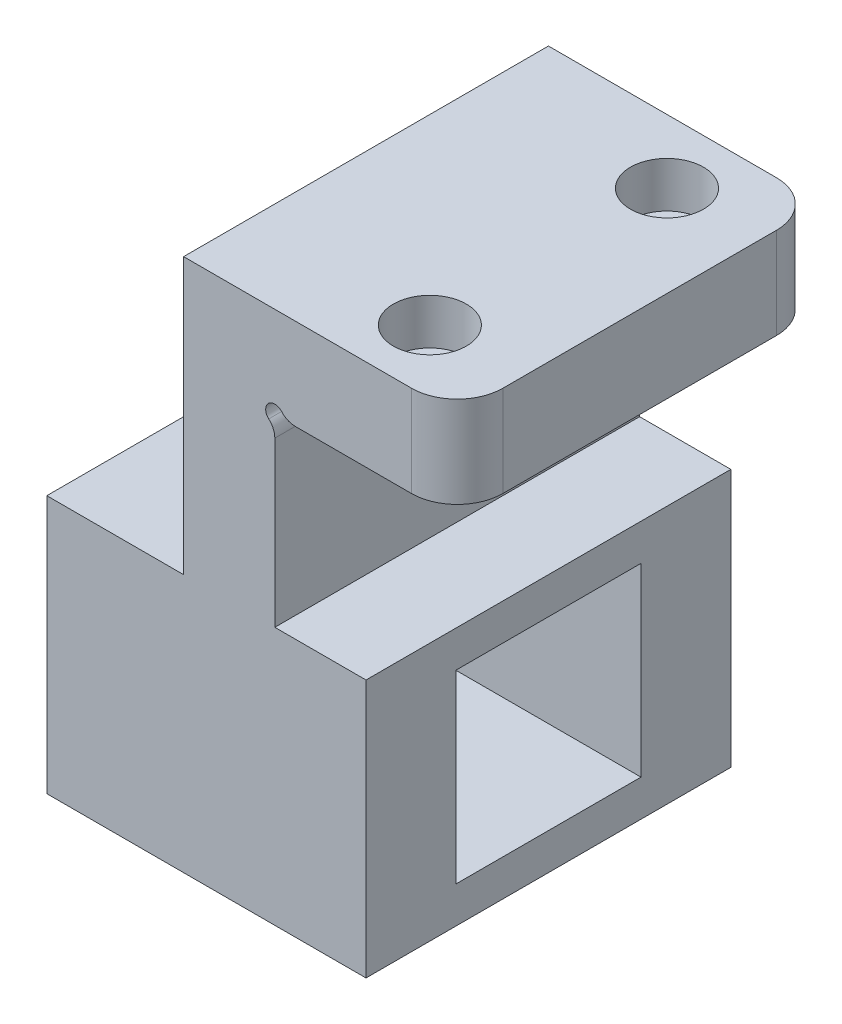
SolidWorks part; units mm, degrees
material "ABS"
ref_plane "Płaszczyzna przednia" through (0, 0, 0) normal (0, 0, 1) x (1, 0, 0)
ref_plane "Płaszczyzna górna" through (0, 0, 0) normal (0, 1, 0) x (1, 0, 0)
ref_plane "Płaszczyzna prawa" through (0, 0, 0) normal (1, 0, 0) x (0, 0, -1)
sketch "Szkic1" plane through (0, 0, 0) normal (0, 0, 1) x (1, 0, 0)
  line L0 (0, 0) -> (0, 19.7639)
  line L1 (2.2361, 22) -> (20, 22)
  line L2 (20, 22) -> (20, 32)
  line L3 (20, 32) -> (-10, 32)
  line L4 (-10, 32) -> (-10, 0)
  line L5 (-10, 0) -> (0, 0)
  arc A0 (0.7454, 22.6667) -> (-0.6667, 21.2546) centre (0, 22) ccw
  arc A1 (2.2361, 22) -> (0.7454, 22.6667) centre (2.2361, 24) cw
  arc A2 (0, 19.7639) -> (-0.6667, 21.2546) centre (-2, 19.7639) ccw
  dimension "D5" = 2
  dimension "D6" = 2
  dimension "D1" = 22
  dimension "D2" = 20
  dimension "D3" = 10
  dimension "D4" = 10
  dimension "D7" = 20
  dimension "D8" = 22
extrude "Dodanie-wyciągnięcie1" add sketch "Szkic1" along normal blind 40 contours L0 A2 A0 A1 L1 L2 L3 L4 L5
sketch "Szkic7" plane through (-10, 0, 0) normal (-1, 0, 0) x (0, 0, 1)
  line L4 (0, 19.7639) -> (0, 0)
  line L5 (40, 19.7639) -> (0, 19.7639)
  line L6 (40, 0) -> (40, 19.7639)
  line L7 (0, 0) -> (40, 0)
  line L8 (0, 19.7639) -> (0, 0)
  line L9 (40, 19.7639) -> (0, 19.7639)
  line L10 (40, 0) -> (40, 19.7639)
  line L11 (0, 0) -> (40, 0)
  circle A0 centre (20, 10) radius 4
  point P7 (20, 0)
  dimension "D2" = 8
  dimension "D3" = 10
  dimension "D1" = 0
extrude "Wytnij-wyciągnięcie2" cut sketch "Szkic7" against normal blind 5 contours A0 region at (-10, 10, 20)
sketch "Szkic8" plane through (-5, 0, 0) normal (-1, 0, 0) x (0, 0, 1)
  circle A0 centre (20, 10) radius 4 construction
  circle A1 centre (20, 10) radius 4
  circle A2 centre (20, 10) radius 2.1
  dimension "D1" = 4.2
extrude "Wytnij-wyciągnięcie3" cut sketch "Szkic8" against normal blind 5 contours A2 region at (-5, 10, 20)
sketch "Szkic9" plane through (0, 32, 0) normal (0, 1, 0) x (1, 0, 0)
  line L4 (20, 0) -> (2.2361, 0)
  line L5 (20, -40) -> (20, 0)
  line L6 (2.2361, -40) -> (20, -40)
  line L7 (2.2361, 0) -> (2.2361, -40)
  line L8 (20, 0) -> (2.2361, 0)
  line L9 (20, -40) -> (20, 0)
  line L10 (2.2361, -40) -> (20, -40)
  line L11 (2.2361, 0) -> (2.2361, -40)
  circle A0 centre (10, -7) radius 4
  circle A1 centre (10, -33) radius 4
  dimension "D3" = 8
  dimension "D2" = 10
  dimension "D4" = 7
  dimension "D5" = 7
  dimension "D1" = 0
extrude "Wytnij-wyciągnięcie4" cut sketch "Szkic9" against normal blind 5 contours A1 | A0 region at (10, 32, 7) region at (10, 32, 33)
sketch "Szkic10" plane through (0, 27, 0) normal (0, 1, 0) x (1, 0, 0)
  circle A0 centre (10, -7) radius 4 construction
  circle A1 centre (10, -33) radius 4 construction
  circle A2 centre (10, -7) radius 4
  circle A3 centre (10, -33) radius 4
  circle A4 centre (10, -7) radius 2.1
  circle A5 centre (10, -33) radius 2.1
  dimension "D1" = 4.2
extrude "Wytnij-wyciągnięcie5" cut sketch "Szkic10" against normal blind 5 contours A5 | A4 region at (10, 27, 7) region at (10, 27, 33)
fillet "Zaokrąglenie1" radius 5 2 edges at (20, 27, 0) (20, 27, 40)
ref_plane "Płaszczyzna1" through (0, 0, 20) normal (0, 0, 1) x (1, 0, 0)
sketch "Sketch1" plane through (-10, 0, 0) normal (-1, 0, 0) x (0, 0, 1)
  line L0 (20, 64.3239) -> (20, 19.1441) construction
  line L1 (9.85, -2.2) -> (30.15, -2.2)
  line L2 (9.85, -2.2) -> (9.85, -22.5)
  line L3 (9.85, -22.5) -> (30.15, -22.5)
  line L4 (30.15, -2.2) -> (30.15, -22.5)
  line L5 (0, 32) -> (0, 0) construction
  line L6 (40, 32) -> (40, 0) construction
  line L7 (40, 22) -> (0, 22) construction
  line L8 (0, 1.8) -> (40, 1.8)
  line L9 (40, 1.8) -> (40, -26.5)
  line L10 (0, -26.5) -> (40, -26.5)
  line L11 (0, 1.8) -> (0, -26.5)
  line L13 (40, 22) -> (0, 22)
  dimension "D1" = 20.3
  dimension "D2" = 20.3
  dimension "D3" = 28.3
  dimension "D4" = 4
  dimension "D5" = 20.2
extrude "Boss-Extrude1" add sketch "Sketch1" along normal blind 15 and the other way blind 20.0001 contours L8 L9 L10 L11 | L1 L4 L3 L2
